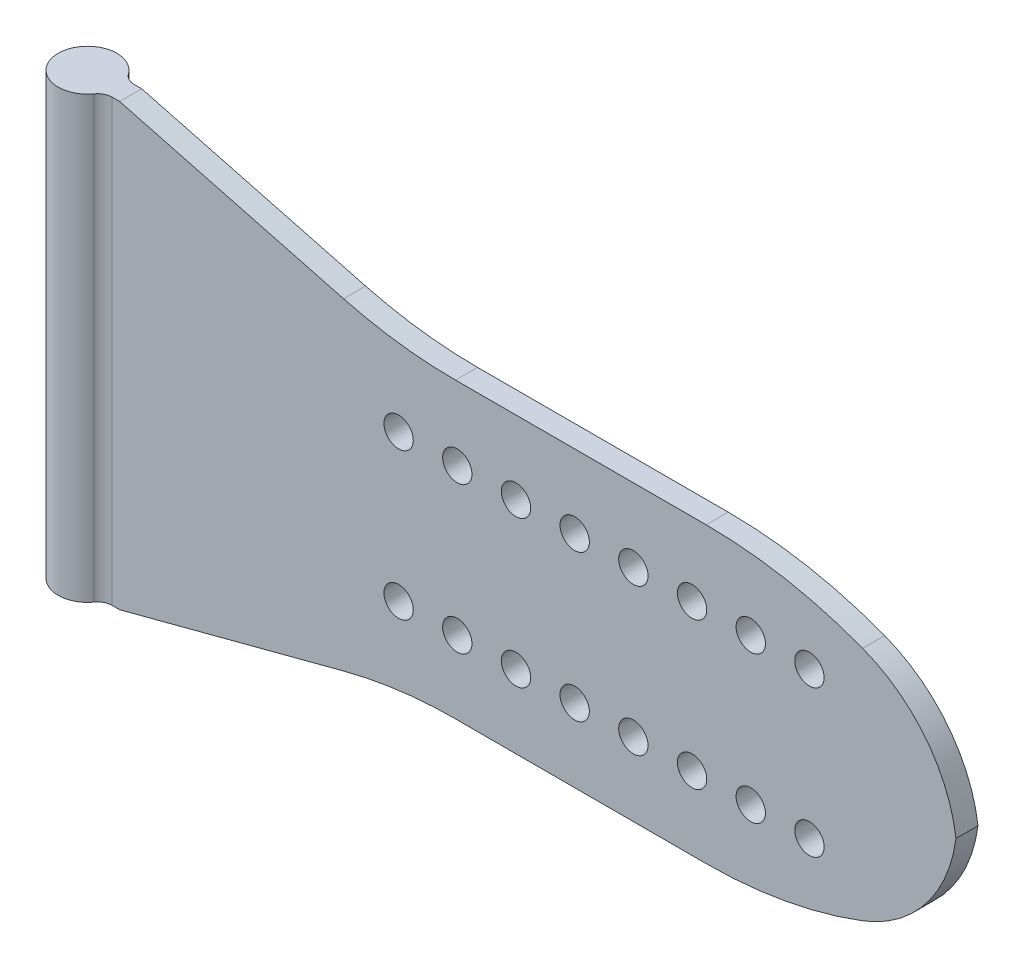
SolidWorks part; units mm, degrees
material "Silicon Rubber"
ref_plane "Front Plane" through (0, 0, 0) normal (0, 0, 1) x (1, 0, 0)
ref_plane "Top Plane" through (0, 0, 0) normal (0, 1, 0) x (1, 0, 0)
ref_plane "Right Plane" through (0, 0, 0) normal (1, 0, 0) x (0, 0, -1)
sketch "Sketch1" plane through (0, 0, 0) normal (0, 1, 0) x (1, 0, 0)
  line L0 (0, 0) -> (2.4367, 0) construction
  line L1 (2.4367, 1.75) -> (2.4367, -1.75) construction
  line L2 (2.4367, 0.75) -> (2.4367, -0.75) construction
  line L3 (2.4367, 0.75) -> (60.0267, 0.75)
  line L4 (60.0267, 0.75) -> (60.0267, -0.75)
  line L5 (60.0267, -0.75) -> (2.4367, -0.75)
  circle A0 centre (0, 0) radius 2 construction
  arc A1 (2.4367, 0.75) -> (1.6245, 1.1667) centre (2.4367, 1.75) cw
  arc A2 (2.4367, -0.75) -> (1.6245, -1.1667) centre (2.4367, -1.75) ccw
  arc A3 (1.6245, 1.1667) -> (1.6245, -1.1667) centre (0, 0) ccw
  point P7 (2.4367, 0)
  point P10 (2.4367, 0)
  dimension "D1" = 4
  dimension "D2" = 1.5
  dimension "D3" = 3.5
  dimension "D4" = 57.59
extrude "Boss-Extrude1" add sketch "Sketch1" along normal blind 15 and the other way blind 15
sketch "Sketch2" plane through (0, 0, 0.75) normal (0, 0, 1) x (1, 0, 0)
  line L0 (60.0267, -5) -> (60.0267, 5) construction
  line L1 (60.0267, -15) -> (60.0267, 15) construction
  line L2 (60.0267, 0) -> (49.9527, 0) construction
  line L3 (49.9527, 10) -> (49.9527, -10) construction
  line L4 (49.9527, 0) -> (2.9407, 0) construction
  line L5 (2.9407, -15) -> (2.9407, 15) construction
  line L6 (2.4367, 15) -> (60.0267, 15) construction
  line L7 (21.9527, 15) -> (21.9527, -15) construction
  line L8 (2.4367, -15) -> (60.0267, -15) construction
  line L9 (60.0267, 5) -> (2.9407, 5) construction
  line L10 (60.0267, -5) -> (2.9407, -5) construction
  line L11 (49.9527, 10) -> (21.9527, 10)
  line L12 (21.9527, 10) -> (2.9407, 15)
  line L13 (2.9407, 15) -> (60.0267, 15)
  line L14 (60.0267, 15) -> (60.0267, 5)
  line L15 (60.0267, 5) -> (49.9527, 10)
  line L16 (49.9527, -10) -> (21.9527, -10)
  line L17 (21.9527, -10) -> (2.9407, -15)
  line L18 (2.9407, -15) -> (60.0267, -15)
  line L19 (60.0267, -15) -> (60.0267, -5)
  line L20 (60.0267, -5) -> (49.9527, -10)
  circle A0 centre (49.9527, 5) radius 1
  circle A1 centre (45.9527, 5) radius 1
  circle A2 centre (41.9527, 5) radius 1
  circle A3 centre (37.9527, 5) radius 1
  circle A4 centre (33.9527, 5) radius 1
  circle A5 centre (29.9527, 5) radius 1
  circle A6 centre (25.9527, 5) radius 1
  circle A7 centre (21.9527, 5) radius 1
  circle A8 centre (45.9527, -5) radius 1
  circle A9 centre (41.9527, -5) radius 1
  circle A10 centre (37.9527, -5) radius 1
  circle A11 centre (33.9527, -5) radius 1
  circle A12 centre (29.9527, -5) radius 1
  circle A13 centre (25.9527, -5) radius 1
  circle A14 centre (21.9527, -5) radius 1
  circle A15 centre (49.9527, -5) radius 1
  point P5 (60.0267, 0)
  point P14 (2.9407, 0)
  point P17 (49.9527, 0)
  point P22 (21.9527, 0)
  dimension "D5" = 2
  dimension "D1" = 10
  dimension "10.074mm" = 10.074
  dimension "D2" = 20
  dimension "D3" = 47.012
  dimension "D4" = 28
  dimension "D6" = 8
  dimension "D7" = 2
extrude "Cut-Extrude1" cut sketch "Sketch2" against normal through all
fillet "Fillet1" radius 30 4 edges at (21.9527, -10, 0) (49.9527, -10, 0) (49.9527, 10, 0) (21.9527, 10, 0)
fillet "Fillet2" radius 10 2 edges at (60.0267, -5, 0) (60.0267, 5, 0)
equation "\"Handle Bar Diameter\"= 4mm'Matching with Strap Clamp"
equation "\"Strap Thickness\"= 1.5mm"
equation "\"D2@Sketch1\"=\"Strap Thickness\""
equation "\"D1@Sketch1\"=\"Handle Bar Diameter\""
